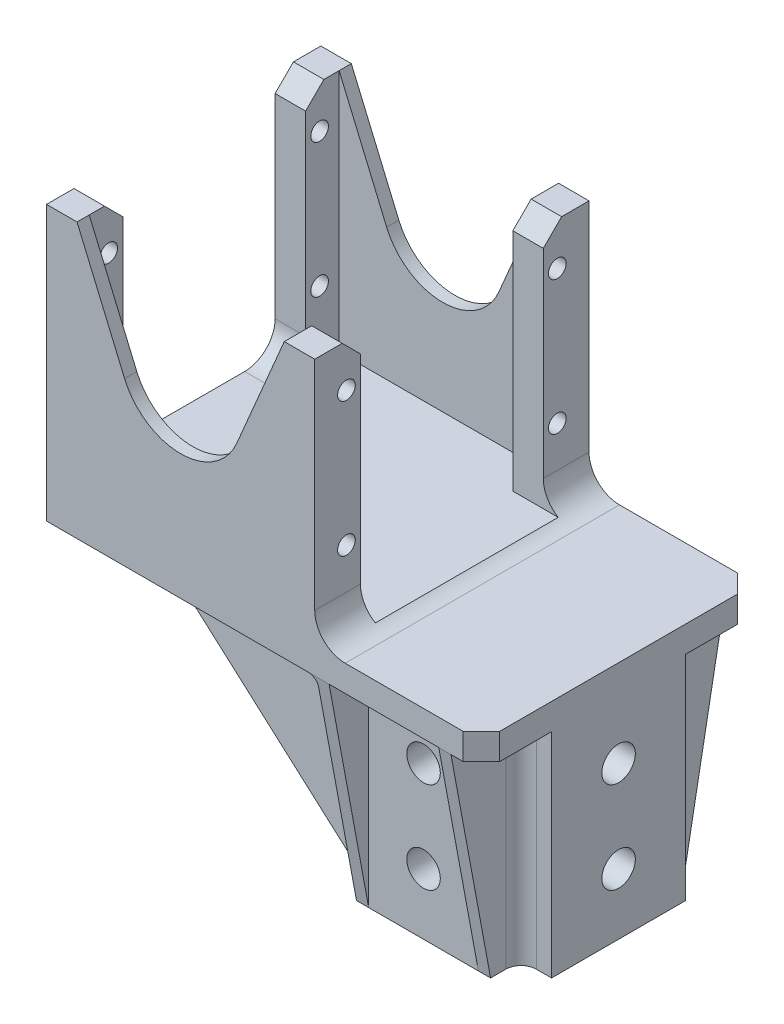
SolidWorks part; units mm, degrees
material "PLA"
ref_plane "Front Plane" through (0, 0, 0) normal (0, 0, 1) x (1, 0, 0)
ref_plane "Top Plane" through (0, 0, 0) normal (0, 1, 0) x (1, 0, 0)
ref_plane "Right Plane" through (0, 0, 0) normal (1, 0, 0) x (0, 0, -1)
sketch "Sketch2" plane through (0, 0, 0) normal (0, 0, 1) x (1, 0, 0)
  line L0 (12.8375, 22.5) -> (17.8375, 22.5) construction
  line L1 (-53.5125, 22.5) -> (17.8375, 22.5) construction
  line L2 (-17.8375, 22.5) -> (-17.8375, -22.5) construction
  line L3 (-53.5125, -22.5) -> (17.8375, -22.5)
  line L4 (17.8375, 22.5) -> (17.8375, -22.5) construction
  line L5 (-17.8375, 22.5) -> (17.8375, -22.5) construction
  line L6 (-17.8375, -22.5) -> (17.8375, 22.5) construction
  line L7 (-48.5125, 22.5) -> (12.8375, 22.5) construction
  line L8 (-17.8375, 22.5) -> (-17.8375, -17.5) construction
  line L9 (-48.5125, -17.5) -> (12.8375, -17.5) construction
  line L10 (12.8375, 22.5) -> (12.8375, -17.5) construction
  line L11 (-17.8375, 22.5) -> (12.8375, -17.5) construction
  line L12 (-17.8375, -17.5) -> (12.8375, 22.5) construction
  line L14 (-17.8375, -17.5) -> (-48.5125, 22.5) construction
  line L15 (-17.8375, 22.5) -> (-48.5125, -17.5) construction
  line L16 (-17.8375, -22.5) -> (-53.5125, 22.5) construction
  line L17 (-17.8375, 22.5) -> (-53.5125, -22.5) construction
  line L18 (-48.5125, 22.5) -> (-48.5125, -17.5)
  line L19 (-53.5125, 22.5) -> (-53.5125, -22.5)
  line L20 (-48.5125, 22.5) -> (-53.5125, 22.5)
  line L22 (-9.5125, -17.5) -> (-9.5125, 22.5)
  line L23 (-9.5125, 22.5) -> (-14.5125, 22.5)
  line L24 (-14.5125, 22.5) -> (-14.5125, -17.5)
  line L26 (17.8375, -17.5) -> (17.8375, -22.5)
  line L27 (-48.5125, -17.5) -> (-14.5125, -17.5)
  line L28 (-9.5125, -17.5) -> (17.8375, -17.5)
  point P4 (0, 0)
  point P8 (-2.5, 2.5)
  point P14 (-33.175, 2.5)
  point P15 (-35.675, 0)
  dimension "D1" = 5
  dimension "D2" = 40
  dimension "D3" = 27.35
  dimension "D4" = 5
  dimension "D5" = 34
  dimension "D6" = 5
extrude "Boss-Extrude1" add sketch "Sketch2" along normal blind 45
sketch "Sketch3" plane through (-53.5125, 0, 0) normal (1, 0, 0) x (0, 0, -1)
  line L0 (-5.2, 22.5) -> (-5.2, -22.5) construction
  line L2 (-39.8, 22.5) -> (-39.8, -22.5) construction
  line L4 (-37.5, 22.5) -> (-7.5, 22.5)
  line L5 (-37.5, 22.5) -> (-37.5, -17.5)
  line L6 (-37.5, -17.5) -> (-7.5, -17.5)
  line L7 (-7.5, 22.5) -> (-7.5, -17.5)
  line L8 (-37.5, 22.5) -> (-7.5, -17.5) construction
  line L9 (-37.5, -17.5) -> (-7.5, 22.5) construction
  line L10 (-45, 22.5) -> (0, 22.5) construction
  line L11 (-39.8, 15.5) -> (-5.2, 15.5) construction
  line L12 (-39.8, -6.5) -> (-5.2, -6.5) construction
  line L13 (-45, -22.5) -> (0, -22.5) construction
  circle A2 centre (-5.2, 15.5) radius 1.25 construction
  circle A3 centre (-5.2, -6.5) radius 1.25 construction
  circle A4 centre (-39.8, 15.5) radius 1.25 construction
  circle A5 centre (-39.8, -6.5) radius 1.25 construction
  point P10 (-22.5, 2.5)
  dimension "D4" = 2.3
  dimension "D7" = 2.5
  dimension "D5" = 2.5
  dimension "D6" = 2.5
  dimension "D9" = 2.5
  dimension "D8" = 22
  dimension "D1" = 30
  dimension "D2" = 5
  dimension "D3" = 2.3
  dimension "D10" = 11
extrude "Cut-Extrude1" cut sketch "Sketch3" along normal through all
sketch "Sketch4" plane through (0, -22.5, 0) normal (0, -1, 0) x (1, 0, 0)
  line L0 (-53.5125, 22.5) -> (17.8375, 22.5) construction
  line L1 (17.8375, 45) -> (17.8375, 0) construction
  line L3 (-53.5125, 45) -> (-53.5125, 0) construction
  line L10 (-8.4125, 32.75) -> (12.0875, 32.75)
  line L11 (-8.4125, 32.75) -> (-8.4125, 12.25)
  line L12 (-8.4125, 12.25) -> (12.0875, 12.25)
  line L13 (12.0875, 32.75) -> (12.0875, 12.25)
  line L14 (-8.4125, 32.75) -> (12.0875, 12.25) construction
  line L15 (-8.4125, 12.25) -> (12.0875, 32.75) construction
  line L16 (-14.1625, 38.5) -> (17.8375, 38.5)
  line L17 (-14.1625, 38.5) -> (-14.1625, 6.5)
  line L18 (-14.1625, 6.5) -> (17.8375, 6.5)
  line L19 (17.8375, 38.5) -> (17.8375, 6.5)
  line L20 (-14.1625, 38.5) -> (17.8375, 6.5) construction
  line L21 (-14.1625, 6.5) -> (17.8375, 38.5) construction
  circle A0 centre (1.8375, 22.5) radius 2.5
  point P18 (1.8375, 22.5)
  point P23 (1.8375, 22.5)
  dimension "D1" = 5
  dimension "D2" = 20.5
  dimension "D3" = 20.5
  dimension "D4" = 32
extrude "Boss-Extrude2" add sketch "Sketch4" along normal blind 35 contours L19 L16 L17 L18 L10 L13 L12 L11 region at (1.8375, -22.5, 38.0475)
sketch "Sketch5" plane through (0, 0, 38.5) normal (0, 0, 1) x (1, 0, 0)
  line L0 (1.8375, -22.5) -> (1.8375, -57.5) construction
  line L3 (-14.1625, -22.5) -> (17.8375, -22.5) construction
  line L4 (-14.1625, -57.5) -> (17.8375, -57.5) construction
  circle A0 centre (1.8375, -32.5) radius 2.5 construction
  circle A1 centre (1.8375, -47.5) radius 2.5 construction
  dimension "D2" = 5
  dimension "D3" = 5
  dimension "D4" = 10
  dimension "D1" = 15
sketch "Sketch6" plane through (0, -57.5, 0) normal (0, -1, 0) x (-1, 0, 0)
  line L1 (14.1625, -38.5) -> (9.1625, -38.5)
  line L2 (14.1625, -38.5) -> (14.1625, -33.5)
  line L3 (14.1625, -33.5) -> (9.1625, -33.5)
  line L4 (9.1625, -38.5) -> (9.1625, -33.5)
  line L5 (14.1625, -38.5) -> (9.1625, -33.5) construction
  line L6 (14.1625, -33.5) -> (9.1625, -38.5) construction
  line L7 (-17.8375, -38.5) -> (-12.8375, -38.5)
  line L8 (-17.8375, -38.5) -> (-17.8375, -33.5)
  line L9 (-17.8375, -33.5) -> (-12.8375, -33.5)
  line L10 (-12.8375, -38.5) -> (-12.8375, -33.5)
  line L11 (-17.8375, -38.5) -> (-12.8375, -33.5) construction
  line L12 (-17.8375, -33.5) -> (-12.8375, -38.5) construction
  line L13 (-17.8375, -6.5) -> (-12.8375, -6.5)
  line L14 (-17.8375, -6.5) -> (-17.8375, -11.5)
  line L15 (-17.8375, -11.5) -> (-12.8375, -11.5)
  line L16 (-12.8375, -6.5) -> (-12.8375, -11.5)
  line L17 (-17.8375, -6.5) -> (-12.8375, -11.5) construction
  line L18 (-17.8375, -11.5) -> (-12.8375, -6.5) construction
  line L19 (14.1625, -6.5) -> (9.1625, -6.5)
  line L20 (14.1625, -6.5) -> (14.1625, -11.5)
  line L21 (14.1625, -11.5) -> (9.1625, -11.5)
  line L22 (9.1625, -6.5) -> (9.1625, -11.5)
  line L23 (14.1625, -6.5) -> (9.1625, -11.5) construction
  line L24 (14.1625, -11.5) -> (9.1625, -6.5) construction
  point P4 (11.6625, -36)
  point P11 (-15.3375, -36)
  point P18 (-15.3375, -9)
  point P25 (11.6625, -9)
  dimension "D1" = 5
  dimension "D2" = 5
  dimension "D3" = 5
  dimension "D4" = 5
extrude "Cut-Extrude4" cut sketch "Sketch6" against normal up to surface (35 mm away) up to face at (-8, -22.5, 22.5)
sketch "Sketch9" plane through (0, 0, 33.5) normal (0, 0, 1) x (1, 0, 0)
  line L0 (-14.1625, -57.5) -> (-53.5125, -22.5)
  line L1 (-53.5125, -22.5) -> (17.8375, -22.5) construction
  line L2 (-53.5125, -22.5) -> (17.8375, -22.5) construction
rib "Rib1" sketch "Sketch9" sketch "Sketch9" thickness 2 extrusion direction parallel to sketch draft on no parameters "D1"=2
pattern_linear "LPattern1" count 2 spacing 20 along (0, 0, -1) of "Rib1"
sketch "Sketch14" plane through (12.8375, 0, 0) normal (1, 0, 0) x (0, 0, -1)
  line L0 (-6.5, -57.5) -> (0, -22.5)
rib "Rib6" sketch "Sketch14" sketch "Sketch14" thickness 2 extrusion direction parallel to sketch draft on no parameters "D1"=2
sketch "Sketch15" plane through (-9.1625, 0, 0) normal (-1, 0, 0) x (0, 0, 1)
  line L0 (6.5, -57.5) -> (0, -22.5)
rib "Rib7" sketch "Sketch15" sketch "Sketch15" thickness 2 extrusion direction parallel to sketch draft on no parameters "D1"=2
fillet "Fillet2" radius 5 3 edges at (-14.1625, -22.5, 22.5) (1.8375, -22.5, 6.5) (1.8375, -22.5, 38.5)
fillet "Fillet3" radius 5 2 edges at (-9.5125, -17.5, 3.75) (-9.5125, -17.5, 41.25)
sketch "Sketch17" plane through (0, 0, 45) normal (0, 0, 1) x (1, 0, 0)
  line L0 (-48.5125, 22.5) -> (-31.5125, -17.5)
  line L1 (-14.5125, -17.5) -> (-48.5125, -17.5) construction
rib "Rib10" sketch "Sketch17" sketch "Sketch17" thickness 2 extrusion direction parallel to sketch draft on no parameters "D1"=2
sketch "Sketch18" plane through (0, 0, 45) normal (0, 0, 1) x (1, 0, 0)
  line L0 (-31.5125, -17.5) -> (-14.5125, 22.5)
rib "Rib11" sketch "Sketch18" sketch "Sketch18" thickness 2 extrusion direction parallel to sketch draft on no parameters "D1"=2
fillet "Fillet4" radius 10 1 edges at (-31.5125, -17.5, 44)
pattern_linear "LPattern2" count 2 spacing 43 along (0, 0, -1) of "Fillet4", "Rib11", "Rib10"
hole_wizard "M5 Clearance Hole2" positions "Sketch20" profile "Sketch22" hole size "M5" standard "ISO"
sketch "Sketch20" plane through (0, 0, 38.5) normal (0, 0, 1) x (1, 0, 0)
  point P0 (1.8375, -32.5)
  point P3 (1.8375, -47.5)
sketch "Sketch22" plane through (1.8375, -32.5, 38.5) normal (1, 0, 0) x (0, -1, 0)
  line L0 (0, 0) -> (0, 7.6524)
  line L1 (0, 7.6524) -> (2.75, 6)
  line L2 (2.75, 6) -> (2.75, 0)
  line L5 (2.75, 0) -> (0, 0)
  line L10 (0, 7.6524) -> (-2.75, 6) construction
  line L11 (0, -6.35) -> (0, 107.95) construction
  dimension "Hole Dia." = 5.5
  dimension "Hole Depth" = 6
  dimension "Drill Angle" = 118
hole_wizard "M2.5 Clearance Hole1" positions "Sketch23" profile "Sketch24" hole size "M2.5" standard "ISO" end condition through all
sketch "Sketch23" plane through (-53.5125, 0, 0) normal (-1, 0, 0) x (0, 0, 1)
  point P0 (5.2, 15.5)
  point P3 (39.8, 15.5)
  point P6 (39.8, -6.5)
  point P9 (5.2, -6.5)
sketch "Sketch24" plane through (-53.5125, 15.5, 5.2) normal (0, 1, 0) x (0, 0, 1)
  line L0 (0, 0) -> (0, 71.35)
  line L1 (0, 71.35) -> (1.45, 71.35)
  line L2 (1.45, 71.35) -> (1.45, 0)
  line L5 (1.45, 0) -> (0, 0)
  line L11 (0, -6.35) -> (0, 107.95) construction
  dimension "Thru Hole Dia." = 2.9
  dimension "Thru Hole Depth" = 71.35
fillet "Fillet5" radius 2.5 4 edges at (-9.1625, -40, 11.5) (-9.1625, -40, 33.5) (12.8375, -40, 33.5) (12.8375, -40, 11.5)
extrude "Boss-Extrude4" add sketch "Sketch4<4>" along normal blind 8 contours A0 region at (1.8375, -22.5, 22.5)
sketch "Sketch4<4>" plane through (0, -22.5, 0) normal (0, -1, 0) x (1, 0, 0) same geometry as "Sketch4"
pattern_circular "CirPattern1" count 4 every 90 about axis through (1.8375, -30.5, 22.5) along (0, -1, 0) of "M5 Clearance Hole2"
ref_axis "Axis2" through (1.8375, -30.5, 22.5) along (0, 1, 0)
ref_plane "Plane1" through (0, 0, 22.5) normal (0, 0, 1) x (1, 0, 0)
mirror "Mirror1" about plane through (0, 0, 22.5) normal (0, 0, 1) of "Rib6", "Rib7"
chamfer "Chamfer1" distance 3 angle 45 6 edges at (17.8375, -20, 0) (17.8375, -20, 45) (-51.0125, 22.5, 37.5) (-51.0125, 22.5, 7.5) (-12.0125, 22.5, 7.5) (-12.0125, 22.5, 37.5)
fillet "Fillet6" radius 5 2 edges at (-51.0125, -17.5, 37.5) (-51.0125, -17.5, 7.5)
fillet "Fillet7" radius 1.5 12 edges at (-9.1625, -22.5, 4.5) (-9.8947, -22.5, 10.7678) (-14.1625, -42.5, 13.5) (-15.627, -23.9645, 13.5) (-14.1625, -42.5, 31.5) (-15.627, -23.9645, 31.5) (-9.1625, -22.5, 40.5) (-9.8947, -22.5, 34.2322) (-32.5875, -22.5, 11.5) (-36.3375, -22.5, 13.5) (-36.3375, -22.5, 31.5) (-32.5875, -22.5, 33.5)
sketch "Sketch27" plane through (0, 0, 45) normal (0, 0, 1) x (1, 0, 0)
  line L0 (17.8375, -17.5) -> (17.8375, -22.5) construction
  line L1 (-9.5125, -12.5) -> (17.8375, -12.5)
  line L2 (-9.5125, -12.5) -> (-9.5125, -18.2)
  line L3 (-9.5125, -18.2) -> (17.8375, -18.2)
  line L4 (17.8375, -12.5) -> (17.8375, -18.2)
  line L5 (10.8375, -22.5) -> (12.8375, -22.5) construction
  dimension "D1" = 4.3
extrude "Cut-Extrude6" cut sketch "Sketch27" against normal through all
fillet "Fillet8" radius 5 1 edges at (-9.5125, -18.2, 22.5)
